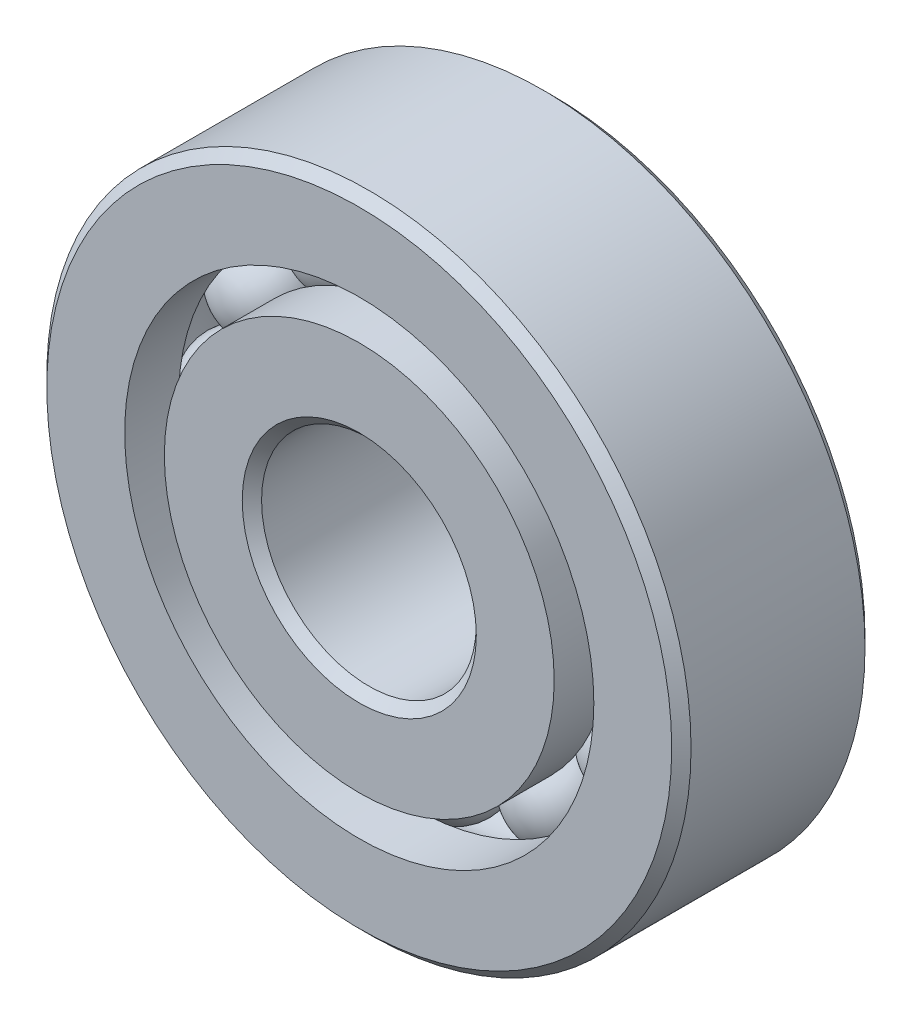
SolidWorks part; units mm, degrees
ref_plane "Front Plane" through (0, 0, 0) normal (0, 0, 1) x (1, 0, 0)
ref_plane "Top Plane" through (0, 0, 0) normal (0, 1, 0) x (1, 0, 0)
ref_plane "Right Plane" through (0, 0, 0) normal (1, 0, 0) x (0, 0, -1)
sketch "Sketch1" plane through (0, 0, 0) normal (1, 0, 0) x (0, 0, -1)
  line L0 (-4.5, 0) -> (4.5, 0) construction
  line L1 (0, 15) -> (0, -15) construction
  line L2 (4.05, 15) -> (-4.05, 15)
  line L3 (-4.05, 15) -> (-4.5, 14.55)
  line L4 (-4.5, 14.55) -> (-4.5, 10.9231)
  line L5 (-4.5, 10.9231) -> (-2, 10.9231)
  line L6 (4.5, 10.9231) -> (2, 10.9231)
  line L7 (4.5, 14.55) -> (4.5, 10.9231)
  line L8 (4.05, 15) -> (4.5, 14.55)
  line L9 (0, 15) -> (0, 10) construction
  line L10 (0, 10) -> (0, 5) construction
  arc A0 (-2, 10.9231) -> (2, 10.9231) centre (0, 10) cw
  point P14 (0, 5)
  dimension "Width" = 9
  dimension "OD" = 30
  dimension "D1" = 45
  dimension "D2" = 0.45
  dimension "Shaft Dia" = 10
  dimension "D3" = 4
  dimension "D4" = 0.9231
revolve "Revolve1" add sketch "Sketch1" angle 360 about L0
sketch "Sketch3" plane through (0, 0, 0) normal (1, 0, 0) x (0, 0, -1)
  line L0 (-4.5, 9.0769) -> (-2, 9.0769)
  line L1 (0, 15) -> (0, -15) construction
  line L2 (-4.5, 14.55) -> (-4.5, 10.9231) construction
  line L3 (-4.5, 9.0769) -> (-4.5, 5.45)
  line L4 (-4.05, 15) -> (-4.5, 14.55) construction
  line L5 (-4.5, 5.45) -> (-4.05, 5)
  line L6 (-4.05, 5) -> (4.05, 5)
  line L7 (4.05, 15) -> (4.05, -15) construction
  line L8 (4.05, 5) -> (4.5, 5.45)
  line L9 (4.5, -14.55) -> (4.5, 14.55) construction
  line L10 (4.5, 5.45) -> (4.5, 9.0769)
  line L11 (4.5, 9.0769) -> (2, 9.0769)
  line L13 (4.05, 15) -> (4.5, 14.55) construction
  arc A0 (2, 10.9231) -> (-2, 10.9231) centre (0, 10) ccw construction
  arc A1 (2, 9.0769) -> (-2, 9.0769) centre (0, 10) cw
revolve "Revolve3" add sketch "Sketch3" angle 360 about L0
sketch "Sketch4" plane through (0, 0, 0) normal (1, 0, 0) x (0, 0, -1)
  line L0 (-2.2027, 10) -> (2.2027, 10)
  arc A2 (-2.2027, 10) -> (2.2027, 10) centre (0, 10) cw
  arc A3 (2, 10.9231) -> (-2, 10.9231) centre (0, 10) ccw construction
revolve "Revolve4" add sketch "Sketch4" angle 360 about L0
ref_axis "Axis1" through (0, 0, -4.5) along (0, 0, 1)
pattern_circular "CirPattern1" count 12 every 30 about axis through (0, 0, -4.5) along (0, 0, 1) of bodies 104
sketch "Sketch5" plane through (0, 0, 0) normal (1, 0, 0) x (0, 0, -1)
  line L0 (-4.5, 10.9231) -> (-2, 10.9231) construction
  line L1 (-4.275, 10.9231) -> (-2.2027, 10.9231)
  line L2 (-4.275, 10.9231) -> (-4.275, 9.0769)
  line L3 (-4.275, 9.0769) -> (-2.2027, 9.0769)
  line L4 (-2.2027, 10.9231) -> (-2.2027, 9.0769)
  line L5 (-4.5, 9.0769) -> (-2, 9.0769) construction
  line L6 (4.5, 10.9231) -> (2, 10.9231) construction
  line L7 (4.275, 10.9231) -> (2.2027, 10.9231)
  line L8 (4.275, 10.9231) -> (4.275, 9.0769)
  line L9 (4.275, 9.0769) -> (2.2027, 9.0769)
  line L10 (2.2027, 10.9231) -> (2.2027, 9.0769)
  line L11 (4.5, 9.0769) -> (2, 9.0769) construction
  line L12 (-4.05, 15) -> (-4.5, 14.55) construction
  point P18 (-4.275, 14.775)
equation "\"D2@Sketch1\" = \"Width@Sketch1\"*.05"
equation "\"D3@Sketch1\" = \"Width@Sketch1\"/2.25"
equation "\"D4@Sketch1\" = (((\"OD@Sketch1\"-\"Width@Sketch1\")/2)/3.25)/3.5"
equation "\"D2@CirPattern1\" = 360/\"Balls@CirPattern1\""
